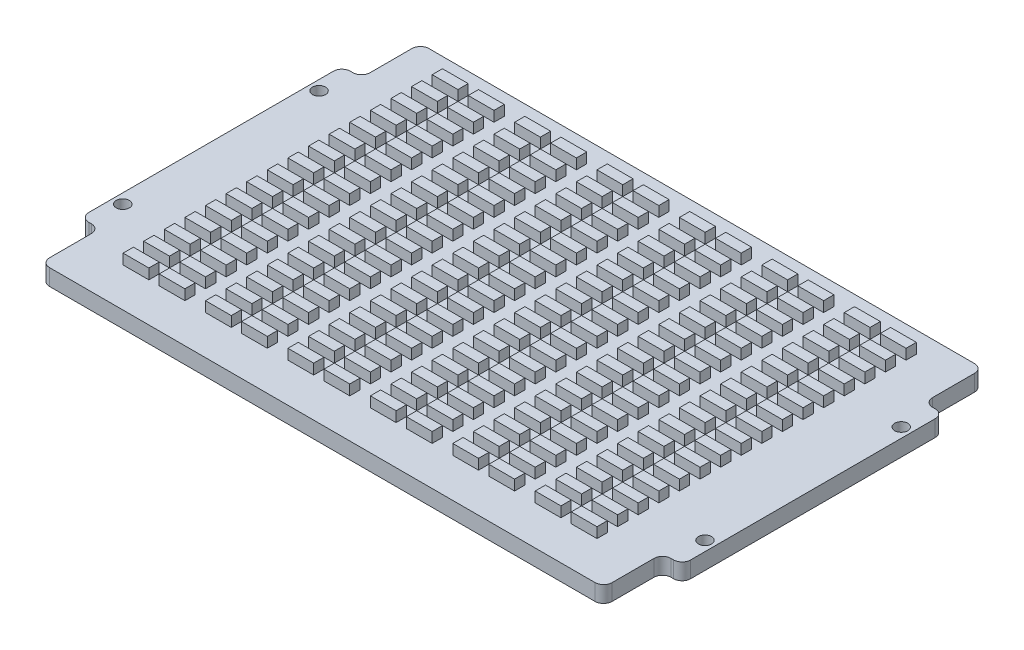
SolidWorks part; units mm, degrees
ref_plane "Front Plane" through (0, 0, 0) normal (0, 0, 1) x (1, 0, 0)
ref_plane "Top Plane" through (0, 0, 0) normal (0, 1, 0) x (1, 0, 0)
ref_plane "Right Plane" through (0, 0, 0) normal (1, 0, 0) x (0, 0, -1)
sketch "Sketch1" plane through (0, 0, 0) normal (0, 1, 0) x (1, 0, 0)
  line L1 (-54.61, -36.83) -> (54.61, -36.83)
  line L2 (-54.61, -36.83) -> (-54.61, 36.83)
  line L3 (-54.61, 36.83) -> (54.61, 36.83)
  line L4 (54.61, -36.83) -> (54.61, 36.83)
  line L5 (-54.61, -36.83) -> (54.61, 36.83) construction
  line L6 (-54.61, 36.83) -> (54.61, -36.83) construction
  point P0 (0, 0)
  dimension "D1" = 109.22
  dimension "D2" = 73.66
extrude "Boss-Extrude1" add sketch "Sketch1" against normal blind 3.175
ref_plane "Plane1" through (0, 0, -31.75) normal (0, 0, 1) x (1, 0, 0)
sketch "Sketch2" plane through (0, 0, -31.75) normal (0, 0, 1) x (1, 0, 0)
  line L3 (-43.75, 0) -> (-46.25, 0)
  line L4 (-43.75, 2) -> (-43.75, 0) construction
  line L5 (-46.25, 0) -> (-46.25, 2)
  line L6 (-54.61, 0) -> (54.61, 0) construction
  line L7 (-41.25, 0) -> (-43.75, 0)
  line L8 (-46.25, 2) -> (-41.25, 2)
  line L9 (-41.25, 2) -> (-41.25, 0)
  line L10 (-39.25, 2) -> (-34.25, 2)
  line L11 (-34.25, 2) -> (-34.25, 0)
  line L12 (-34.25, 0) -> (-36.75, 0)
  line L13 (-39.25, 0) -> (-39.25, 2)
  line L14 (-39.25, 0) -> (-36.75, 0)
  point P5 (-45, 0)
  dimension "D1" = 2.5
  dimension "D2" = 2
  dimension "D3" = 45
  dimension "D4" = 2
  dimension "D5" = 2
  dimension "D6" = 5
extrude "Boss-Extrude3" add sketch "Sketch2" along normal mid plane 2
pattern_linear "LPattern1" count 6 spacing 16 along (1, 0, 0) count 16 spacing 4 along (0, 0, 1) of "Boss-Extrude3"
sketch "Sketch3" plane through (0, 0, 0) normal (0, 1, 0) x (1, 0, 0)
  line L0 (-54.61, 36.83) -> (-54.61, -36.83) construction
  line L1 (-54.61, 25.4) -> (-58.42, 25.4)
  line L2 (-54.61, 25.4) -> (-54.61, -25.4)
  line L3 (-54.61, -25.4) -> (-58.42, -25.4)
  line L4 (-58.42, 25.4) -> (-58.42, -25.4)
  line L5 (0, 0) -> (0, 36.83) construction
  line L6 (54.61, 36.83) -> (-54.61, 36.83) construction
  line L7 (58.42, 25.4) -> (58.42, -25.4)
  line L8 (54.61, -25.4) -> (58.42, -25.4)
  line L9 (54.61, 25.4) -> (54.61, -25.4)
  line L10 (54.61, 25.4) -> (58.42, 25.4)
  circle A0 centre (-56.515, 19.05) radius 1.27
  circle A1 centre (-56.515, -19.05) radius 1.27
  circle A2 centre (56.515, -19.05) radius 1.27
  circle A3 centre (56.515, 19.05) radius 1.27
  point P6 (-58.42, 0)
  point P11 (-56.515, 25.4)
  dimension "D3" = 2.54
  dimension "D1" = 3.81
  dimension "D2" = 50.8
  dimension "D4" = 19.05
  dimension "D5" = 2
extrude "Boss-Extrude2" add sketch "Sketch3" against normal blind 3.175
fillet "Fillet1" radius 1.651 12 edges at (54.61, -1.5875, -36.83) (54.61, -1.5875, -25.4) (58.42, -1.5875, -25.4) (58.42, -1.5875, 25.4) (54.61, -1.5875, 25.4) (54.61, -1.5875, 36.83) (-54.61, -1.5875, 36.83) (-54.61, -1.5875, 25.4) (-58.42, -1.5875, 25.4) (-58.42, -1.5875, -25.4) (-54.61, -1.5875, -25.4) (-54.61, -1.5875, -36.83)
